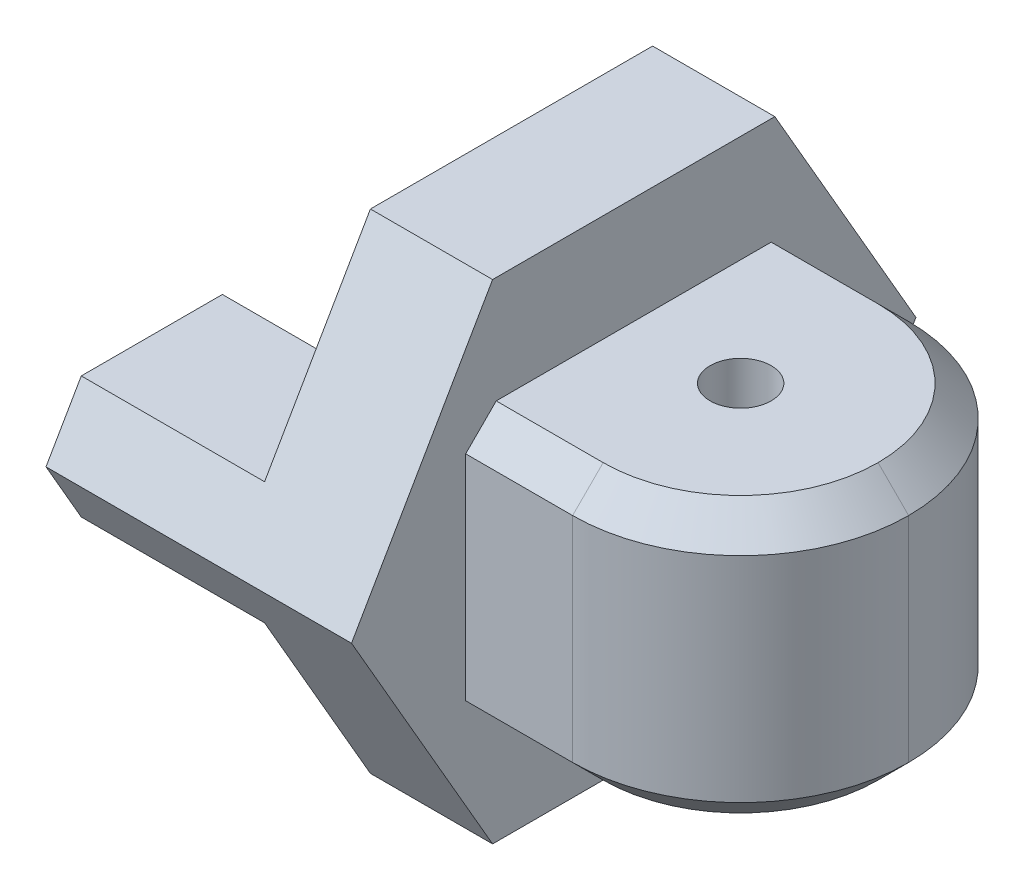
SolidWorks part; units mm, degrees
ref_plane "정면" through (0, 0, 0) normal (0, 0, 1) x (1, 0, 0)
ref_plane "윗면" through (0, 0, 0) normal (0, 1, 0) x (1, 0, 0)
ref_plane "우측면" through (0, 0, 0) normal (1, 0, 0) x (0, 0, -1)
sketch "스케치2" plane through (0, 0, 0) normal (1, 0, 0) x (0, 0, -1)
  line L1 (46.188, 0) -> (23.094, 40)
  line L2 (23.094, 40) -> (-23.094, 40)
  line L3 (-23.094, 40) -> (-46.188, 0)
  line L4 (-46.188, 0) -> (-23.094, -40)
  line L5 (-23.094, -40) -> (23.094, -40)
  line L6 (23.094, -40) -> (46.188, 0)
  circle A0 centre (0, 0) radius 40 construction
  circle A1 centre (0, 0) radius 20
extrude "보스-돌출1" add sketch "스케치2" along normal blind 50
sketch "스케치3" plane through (0, 0, 0) normal (-1, 0, 0) x (0, 0, 1)
  line L1 (-46.188, 0) -> (47.8081, 0)
  line L2 (-46.188, 0) -> (-46.188, 10)
  line L3 (-46.188, 10) -> (47.8081, 10)
  line L4 (47.8081, 0) -> (47.8081, 10)
  line L5 (-46.188, 0) -> (47.8081, 0)
  line L6 (-46.188, 0) -> (-46.188, -10)
  line L7 (-46.188, -10) -> (47.8081, -10)
  line L8 (47.8081, 0) -> (47.8081, -10)
  line L9 (-46.188, 10) -> (47.8081, 10)
  line L10 (-46.188, 10) -> (-46.188, 40.6369)
  line L11 (-46.188, 40.6369) -> (47.8081, 40.6369)
  line L12 (47.8081, 10) -> (47.8081, 40.6369)
  line L13 (-46.188, -10) -> (47.8081, -10)
  line L14 (-46.188, -10) -> (-46.188, -40.6369)
  line L15 (-46.188, -40.6369) -> (47.8081, -40.6369)
  line L16 (47.8081, -10) -> (47.8081, -40.6369)
  line M1 (-46.188, 0) -> (-23.094, -40)
  line M2 (-23.094, -40) -> (23.094, -40)
  line M3 (23.094, -40) -> (46.188, 0)
  line M4 (46.188, 0) -> (23.094, 40)
  line M5 (23.094, 40) -> (-23.094, 40)
  line M6 (-23.094, 40) -> (-46.188, 0)
  circle M7 centre (0, 0) radius 20
  dimension "D1" = 10
  dimension "D2" = 10
sketch "스케치4" plane through (0, 0, 0) normal (-1, 0, 0) x (0, 0, 1)
extrude "컷-돌출2" cut sketch "스케치3" against normal blind 30 contours L3 M6 M7 M4 M5 region at (0, 25.048, 0)
extrude "컷-돌출3" cut sketch "스케치3<4>" against normal blind 30 contours L7 M1 M2 M3 M7 region at (0, -25.048, 0)
sketch "스케치3<4>" plane through (0, 0, 0) normal (-1, 0, 0) x (0, 0, 1) same geometry as "스케치3"
sketch "스케치5" plane through (50, 0, 0) normal (1, 0, 0) x (0, 0, -1)
  line L1 (-27.5, -22.5) -> (27.5, -22.5)
  line L2 (-27.5, -22.5) -> (-27.5, 22.5)
  line L3 (-27.5, 22.5) -> (27.5, 22.5)
  line L4 (27.5, -22.5) -> (27.5, 22.5)
  line L5 (-27.5, -22.5) -> (27.5, 22.5) construction
  line L6 (-27.5, 22.5) -> (27.5, -22.5) construction
  point P0 (0, 0)
  dimension "D1" = 55
  dimension "D2" = 45
extrude "보스-돌출2" add sketch "스케치5" along normal blind 45 contours L4 L3 L2 L1
fillet "필렛2" radius 27.5 1 edges at (95, 0, -27.5)
fillet "필렛3" radius 27.5 1 edges at (95, 0, 27.5)
chamfer "모따기1" distance 5 angle 45 4 edges at (58.75, -22.5, 27.5) (86.9454, -22.5, 19.4454) (86.9454, -22.5, -19.4454) (58.75, -22.5, -27.5)
sketch "스케치6" plane through (0, -22.5, 0) normal (0, -1, 0) x (1, 0, 0)
  line L0 (90, 0) -> (50, 0) construction
  line L1 (50, 22.5) -> (50, -22.5) construction
  line L2 (67.5, -22.5) -> (67.5, 22.5) construction
  arc A0 (67.5, -22.5) -> (90, 0) centre (67.5, 0) ccw construction
  circle A1 centre (67.5, 0) radius 5
extrude "컷-돌출4" cut sketch "스케치6" against normal through all contours A1
chamfer "모따기2" distance 5 angle 45 4 edges at (58.75, 22.5, 27.5) (86.9454, 22.5, 19.4454) (58.75, 22.5, -27.5) (86.9454, 22.5, -19.4454)
